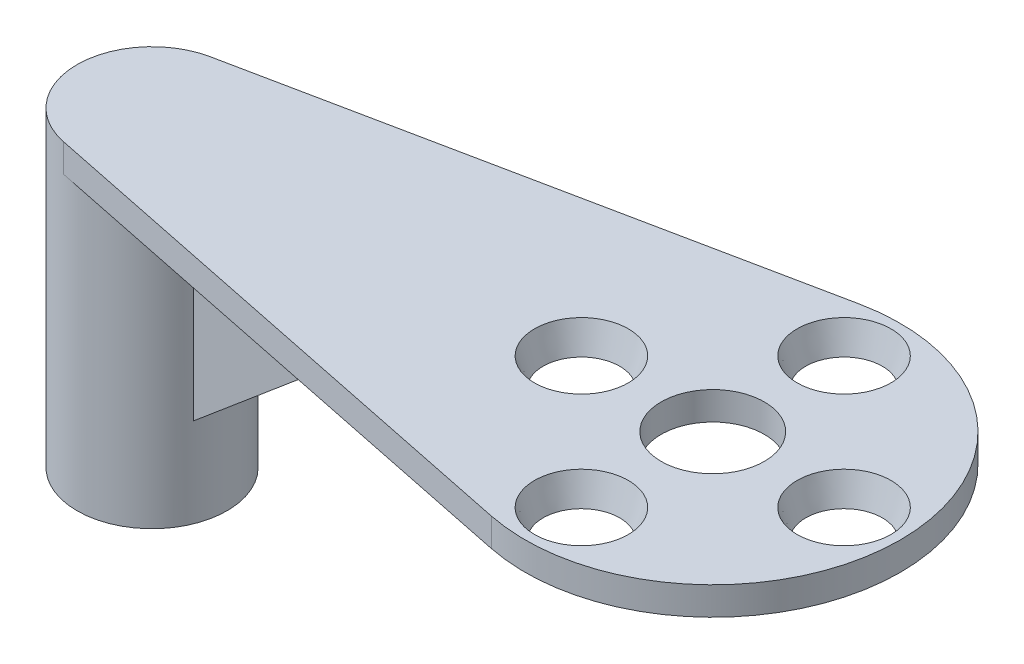
SolidWorks part; units mm, degrees
ref_plane "Front Plane" through (0, 0, 0) normal (0, 0, 1) x (1, 0, 0)
ref_plane "Top Plane" through (0, 0, 0) normal (0, 1, 0) x (1, 0, 0)
ref_plane "Right Plane" through (0, 0, 0) normal (1, 0, 0) x (0, 0, -1)
sketch "Croquis1" plane through (0, 0, 0) normal (0, 1, 0) x (1, 0, 0)
  line L0 (-0.8029, 3.9186) -> (27.8826, 9.7965)
  line L3 (-0.8029, -3.9186) -> (27.8826, -9.7965)
  arc A1 (27.8826, -9.7965) -> (27.8826, 9.7965) centre (29.89, 0) ccw
  arc A4 (-0.8029, 3.9186) -> (-0.8029, -3.9186) centre (0, 0) ccw
  circle A5 centre (29.89, 7) radius 1.6
  circle A7 centre (36.89, 0) radius 1.6
  circle A8 centre (29.89, -7) radius 1.6
  circle A9 centre (22.89, 0) radius 1.6
  circle A10 centre (29.89, 0) radius 2.75
  dimension "D1" = 20
  dimension "D3" = 8
  dimension "D5" = 3.2
  dimension "D7" = 5.5
  dimension "D2" = 29.89
  dimension "D4" = 7
  dimension "D6" = 4
extrude "Saliente-Extruir1" add sketch "Croquis1" along normal blind 1.5
sketch "Croquis3" plane through (0, 0, 0) normal (0, -1, 0) x (1, 0, 0)
  circle A3 centre (0, 0) radius 4
  arc A4 (-0.8029, 3.9186) -> (-0.8029, -3.9186) centre (0, 0) ccw construction
extrude "Saliente-Extruir3" add sketch "Croquis3" along normal offset from surface (15.1 mm away) 16.6 up to face at (29.89, 1.5, 8.6)
sketch "Croquis4" plane through (0, -15.1, 0) normal (0, -1, 0) x (1, 0, 0)
  circle A0 centre (0, 0) radius 2.5
  circle A1 centre (0, 0) radius 3.1
  dimension "D1" = 5
  dimension "D2" = 6.2
extrude "Cortar-Extruir1" cut sketch "Croquis4" against normal blind 7.87 contours A1
extrude "Saliente-Extruir4" add sketch "Croquis4<3>" against normal offset from surface (6.17 mm away) 0.85 from offset 0.85 up to face at (0, -7.23, -3.1) offset against normal yes
sketch "Croquis4<3>" plane through (0, -15.1, 0) normal (0, -1, 0) x (1, 0, 0) same geometry as "Croquis4"
sketch "Croquis5" plane through (0, 1.5, 0) normal (0, 1, 0) x (1, 0, 0)
  circle A0 centre (29.89, 7) radius 2.5
  circle A1 centre (29.89, 0) radius 10
  arc A2 (27.8826, -9.7965) -> (27.8826, 9.7965) centre (29.89, 0) ccw construction
  circle A3 centre (36.89, 0) radius 2.5
  circle A4 centre (29.89, -7) radius 2.5
  circle A5 centre (22.89, 0) radius 2.5
  dimension "D1" = 5
  dimension "D2" = 4
extrude "Cortar-Extruir3" cut sketch "Croquis5" against normal blind 1.5 draft 17 contours A4 | A3 | A0 | A5
sketch "Croquis6" plane through (0, 0, 0) normal (0, 0, 1) x (1, 0, 0)
  line L0 (16, 0) -> (4, -10.1)
  line L1 (-0.8029, 0) -> (27.8826, 0) construction
  line L2 (4, -15.1) -> (4, 0) construction
  line L3 (-4, -15.1) -> (4, -15.1) construction
  point P6 (15.4234, 0)
  dimension "D1" = 5
  dimension "D2" = 12
rib "Nervio1" sketch "Croquis6" sketch "Croquis6" thickness 3 extrusion direction parallel to sketch draft on no parameters "D1"=3
sketch "Croquis7" plane through (0, 1.5, 0) normal (0, 1, 0) x (1, 0, 0)
  line L0 (-4, 0) -> (39.89, 0) construction
  arc A0 (-0.8029, 3.9186) -> (-0.8029, -3.9186) centre (0, 0) ccw construction
  arc A1 (27.8826, -9.7965) -> (27.8826, 9.7965) centre (29.89, 0) ccw construction
